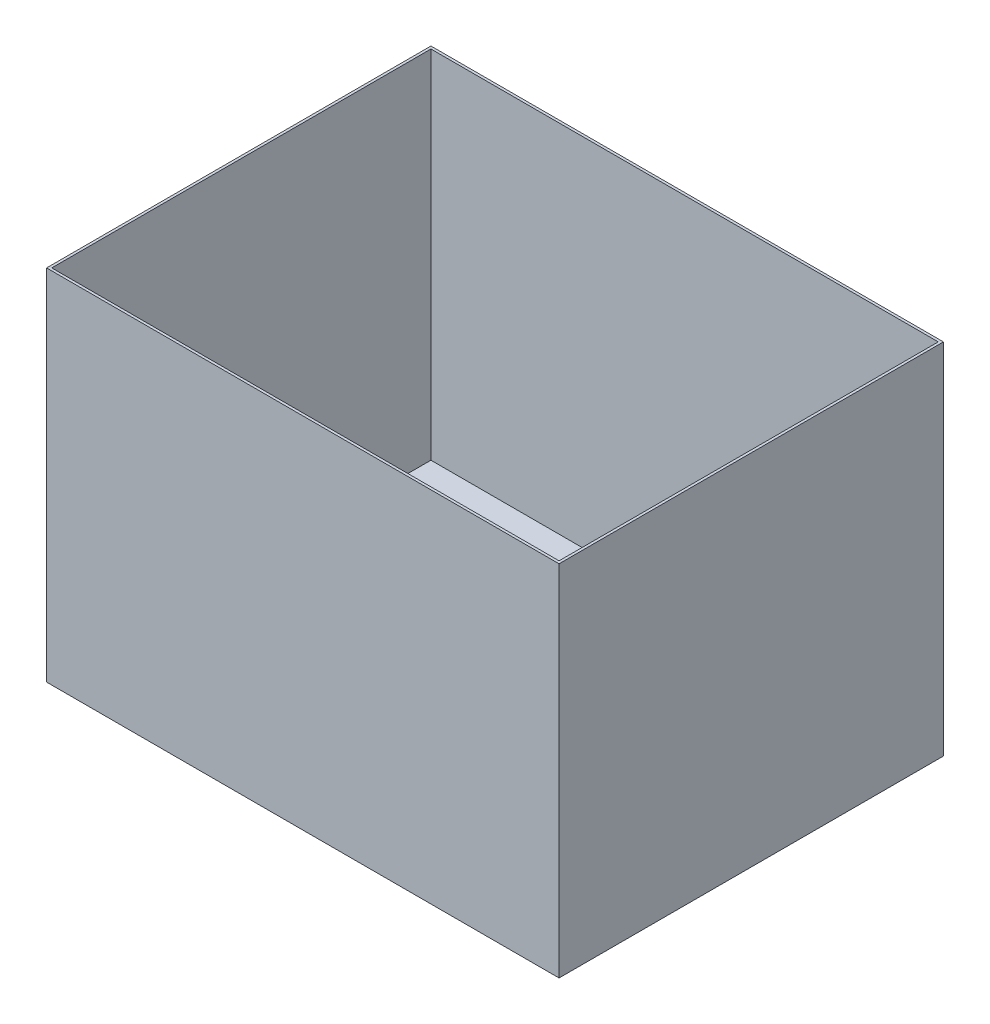
SolidWorks part; units mm, degrees
ref_plane "前视基准面" through (0, 0, 0) normal (0, 0, 1) x (1, 0, 0)
ref_plane "上视基准面" through (0, 0, 0) normal (0, 1, 0) x (1, 0, 0)
ref_plane "右视基准面" through (0, 0, 0) normal (1, 0, 0) x (0, 0, -1)
sketch "草图1" plane through (0, 0, 0) normal (0, 1, 0) x (1, 0, 0)
  line L0 (-200, 150) -> (200, -150) construction
  line L1 (-200, -150) -> (200, -150)
  line L2 (-200, -150) -> (-200, 150)
  line L3 (-200, 150) -> (200, 150)
  line L4 (200, -150) -> (200, 150)
  line L5 (200, 150) -> (-200, -150) construction
  point P5 (0, 0)
  dimension "D1" = 400
  dimension "D2" = 300
extrude "网" add sketch "草图1" along normal blind 2 contours L2 L3 L4 L1
extrude "网纵" add sketch "草图1<3>" along normal blind 280 thin thin type one direction reverse wall 2
sketch "草图1<3>" plane through (0, 0, 0) normal (0, 1, 0) x (1, 0, 0) same geometry as "草图1"
